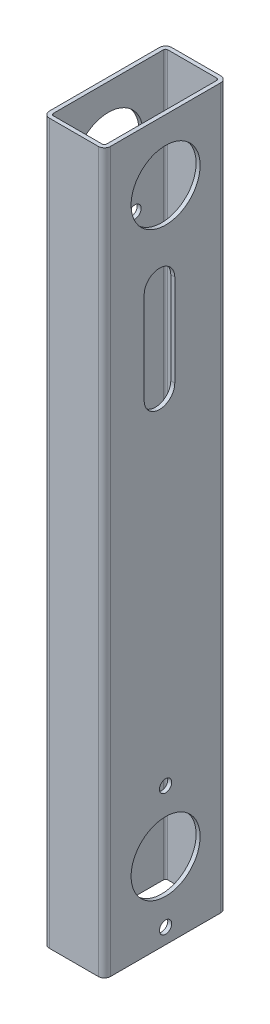
SolidWorks part; units mm, degrees
material "6061-T6 (SS)"
ref_plane "Front Plane" through (0, 0, 0) normal (0, 0, 1) x (1, 0, 0)
ref_plane "Top Plane" through (0, 0, 0) normal (0, 1, 0) x (1, 0, 0)
ref_plane "Right Plane" through (0, 0, 0) normal (1, 0, 0) x (0, 0, -1)
sketch "Sketch1" plane through (0, 0, 0) normal (0, 1, 0) x (1, 0, 0)
  line L1 (10.16, -25.4) -> (-10.16, -25.4)
  line L2 (12.7, -22.86) -> (12.7, 22.86)
  line L3 (10.16, 25.4) -> (-10.16, 25.4)
  line L4 (-12.7, -22.86) -> (-12.7, 22.86)
  line L5 (12.7, -25.4) -> (-12.7, 25.4) construction
  line L6 (12.7, 25.4) -> (-12.7, -25.4) construction
  arc A0 (-10.16, -25.4) -> (-12.7, -22.86) centre (-10.16, -22.86) cw
  arc A1 (10.16, -25.4) -> (12.7, -22.86) centre (10.16, -22.86) ccw
  arc A2 (12.7, 22.86) -> (10.16, 25.4) centre (10.16, 22.86) ccw
  arc A3 (-10.16, 25.4) -> (-12.7, 22.86) centre (-10.16, 22.86) ccw
  point P0 (0, 0)
  dimension "D3" = 2.54
  dimension "D1" = 25.4
  dimension "D2" = 50.8
extrude "Extrude-Thin1" add sketch "Sketch1" along normal blind 222.25 and the other way blind 76.2 thin thin type one direction reverse wall 1.651
sketch "Sketch2" plane through (-12.7, 0, 0) normal (-1, 0, 0) x (0, 0, 1)
  line L0 (2.54, 161.9426) -> (2.54, 12.7) construction
  line L4 (9.2075, 161.9426) -> (9.2075, 12.7)
  line L5 (-4.1275, 161.9426) -> (-4.1275, 12.7)
  line L6 (2.54, 25.4) -> (2.54, 149.2426) construction
  arc A2 (9.2075, 161.9426) -> (-4.1275, 161.9426) centre (2.54, 161.9426) ccw
  arc A3 (-4.1275, 12.7) -> (9.2075, 12.7) centre (2.54, 12.7) ccw
  point P3 (2.54, 87.3213)
  dimension "D5" = 13.335
  dimension "D2" = 12.7
  dimension "D1" = 12.7
extrude "Cut-Extrude1" cut sketch "Sketch2" against normal up to next
sketch "Sketch5" plane through (12.7, 0, 0) normal (1, 0, 0) x (0, 0, -1)
  line L0 (-2.54, 161.9426) -> (-2.54, 123.8426) construction
  line L1 (3.81, 161.9426) -> (3.81, 123.8426)
  line L2 (-8.89, 161.9426) -> (-8.89, 123.8426)
  arc A0 (3.81, 161.9426) -> (-8.89, 161.9426) centre (-2.54, 161.9426) ccw
  arc A1 (-8.89, 123.8426) -> (3.81, 123.8426) centre (-2.54, 123.8426) ccw
  arc A2 (4.1275, 161.9426) -> (-9.2075, 161.9426) centre (-2.54, 161.9426) ccw construction
  point P2 (-2.54, 142.8926)
  dimension "D1" = 6.35
  dimension "D2" = 38.1
extrude "Cut-Extrude4" cut sketch "Sketch5" against normal up to next
sketch "Sketch4" plane through (-12.7, 0, 0) normal (1, 0, 0) x (0, 0, -1)
  circle A12 centre (11.049, 4.7713) radius 2.5527
  circle A13 centre (-16.129, 4.7713) radius 2.5527
  circle A14 centre (-16.129, 87.3213) radius 2.5527
  circle A15 centre (11.049, 87.3213) radius 2.5527
  circle A16 centre (-16.129, 169.8713) radius 2.5527
  circle A17 centre (11.049, 169.8713) radius 2.5527
  dimension "D1" = 5.1054
extrude "Cut-Extrude3" cut sketch "Sketch4" along normal up to surface (1.651 mm away) up to face at (-11.049, 87.3213, 2.54)
sketch "Sketch6" plane through (12.7, 0, 0) normal (1, 0, 0) x (0, 0, -1)
  line L0 (25.4, -76.2) -> (25.4, 222.25) construction
  circle A0 centre (0, -44.45) radius 14.3256
  circle A1 centre (0, 196.85) radius 14.3256
  point P7 (0, 0)
  dimension "D1" = 28.6512
  dimension "D2" = 25.4
  dimension "D3" = 44.45
  dimension "D4" = 241.3
extrude "Cut-Extrude5" cut sketch "Sketch6" against normal through all
hole_wizard "#10 Clearance Hole1" positions "Sketch8" profile "Sketch9" hole size "#10" standard "ANSI Inch" end condition through all
sketch "Sketch8" plane through (12.7, 0, 0) normal (1, 0, 0) x (0, 0, -1)
  circle A0 centre (0, -44.45) radius 25.4 construction
  point P0 (0, -19.05)
  point P11 (0, -69.85)
  dimension "D1" = 50.8
sketch "Sketch9" plane through (12.7, -19.05, 0) normal (0, 1, 0) x (0, 0, -1)
  line L0 (0, 0) -> (0, 25.4)
  line L1 (0, 25.4) -> (2.5527, 25.4)
  line L2 (2.5527, 25.4) -> (2.5527, 0)
  line L5 (2.5527, 0) -> (0, 0)
  line L11 (0, -6.35) -> (0, 107.95) construction
  dimension "Thru Hole Dia." = 5.1054
  dimension "Thru Hole Depth" = 25.4
